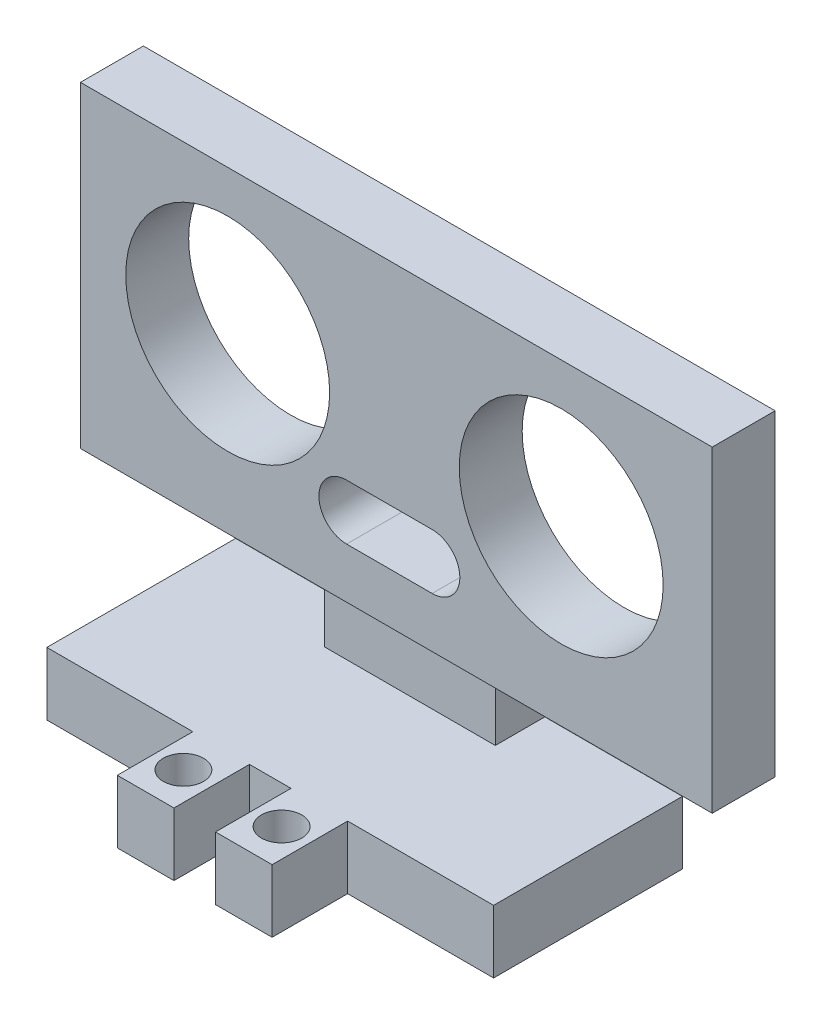
SolidWorks part; units mm, degrees
ref_plane "Front Plane" through (0, 0, 0) normal (0, 0, 1) x (1, 0, 0)
ref_plane "Top Plane" through (0, 0, 0) normal (0, 1, 0) x (1, 0, 0)
ref_plane "Right Plane" through (0, 0, 0) normal (1, 0, 0) x (0, 0, -1)
sketch "Sketch1" plane through (0, 0, 0) normal (0, 1, 0) x (1, 0, 0)
  line L0 (12.7692, 9.9599) -> (48.2692, 9.9599)
  line L5 (12.7692, 21.2754) -> (24.3692, 21.2754)
  line L10 (12.7692, 21.2754) -> (12.7692, 6.2754)
  line L11 (12.7692, 6.2754) -> (24.3692, 6.2754)
  line L12 (48.2692, 21.2754) -> (48.2692, 6.2754)
  line L13 (12.7692, 14.0701) -> (48.2692, 14.1179)
  line L21 (28.8692, 21.2754) -> (32.1692, 21.2754)
  line L22 (36.6692, 21.2754) -> (48.2692, 21.2754)
  line L23 (24.3692, 21.2754) -> (28.8692, 21.2754)
  line L24 (32.1692, 21.2754) -> (36.6692, 21.2754)
  line L25 (24.3692, 0.2754) -> (24.3692, 6.2754)
  line L26 (24.3692, 0.2754) -> (28.8692, 0.2754)
  line L27 (28.8692, 0.2754) -> (28.8692, 6.2754)
  line L28 (32.1692, 0.2754) -> (32.1692, 6.2754)
  line L29 (32.1692, 0.2754) -> (36.6692, 0.2754)
  line L30 (36.6692, 0.2754) -> (36.6692, 6.2754)
  line L31 (28.8692, 6.2754) -> (32.1692, 6.2754)
  line L32 (36.6692, 6.2754) -> (48.2692, 6.2754)
  dimension "D3" = 3.3
  dimension "D4" = 11.6
  dimension "D5" = 4.5
  dimension "D6" = 4.5
  dimension "D1" = 35.5
  dimension "D2" = 15
  dimension "D7" = 6
  dimension "D8" = 6
extrude "Boss-Extrude7" add sketch "Sketch1" along normal blind 5 contours L13 L12 L5 L10 | L13 L10 L0 L12 | L0 L10 L11 L12 region at (30.5534, 0, -12.0269) region at (30.5192, 0, -6.7027) region at (30.4995, 0, -17.6847)
sketch "Sketch5" plane through (0, 5, 0) normal (0, 1, 0) x (1, 0, 0)
  line L0 (12.7692, 21.2754) -> (48.2692, 21.2754) construction
  line L1 (23.7692, 21.2754) -> (37.3363, 21.2754)
  line L2 (23.7692, 21.2754) -> (23.7692, 17.3426)
  line L3 (23.7692, 17.3426) -> (37.3363, 17.3426)
  line L4 (37.3363, 21.2754) -> (37.3363, 17.3426)
  line L5 (12.7692, 21.2754) -> (12.7692, 6.2754) construction
  dimension "D1" = 11
  dimension "D2" = 13.5671
extrude "Boss-Extrude8" add sketch "Sketch5" along normal blind 5
sketch "Sketch6" plane through (1.1246, 10, 0) normal (0, 1, 0) x (1, 0, 0)
  line L0 (11.6446, 21.2754) -> (11.6446, 6.2754) construction
  line L2 (4.2946, 21.2948) -> (54.4946, 21.2948)
  line L3 (4.2946, 21.2948) -> (4.2946, 16.2948)
  line L4 (4.2946, 16.2948) -> (54.4946, 16.2948)
  line L5 (54.4946, 21.2948) -> (54.4946, 16.2948)
  dimension "D1" = 50.2
  dimension "D2" = 5
  dimension "D3" = 7.35
extrude "Boss-Extrude9" add sketch "Sketch6" along normal blind 25.2 contours L3 L2 L5 L4
sketch "Sketch7" plane through (0, 0, -16.2948) normal (0, 0, 1) x (1, 0, 0)
  line L0 (17.1192, 23.75) -> (43.6192, 23.75)
  line L1 (5.4192, 10) -> (55.6192, 10) construction
  line L2 (26.5664, 16.2) -> (33.3664, 16.2) construction
  line L3 (26.5664, 18.4) -> (33.3664, 18.4)
  line L4 (26.5664, 14) -> (33.3664, 14)
  line L5 (55.6192, 35.2) -> (55.6192, 10) construction
  circle A0 centre (17.1192, 23.75) radius 8.1
  circle A1 centre (43.6192, 23.75) radius 8.1
  arc A2 (26.5664, 18.4) -> (26.5664, 14) centre (26.5664, 16.2) ccw
  arc A3 (33.3664, 14) -> (33.3664, 18.4) centre (33.3664, 16.2) ccw
  point P8 (29.9664, 16.2)
  dimension "D1" = 16.2
  dimension "D4" = 2.2
  dimension "D7" = 12
  dimension "D2" = 26.5
  dimension "D3" = 6.8
  dimension "D5" = 5.35
  dimension "D6" = 4
  dimension "D8" = 10.2528
extrude "Cut-Extrude1" cut sketch "Sketch7" against normal blind 10 contours A0 | A1 region at (43.6192, 31.6209, -16.2948) region at (9.2483, 23.75, -16.2948)
extrude "Cut-Extrude2" cut sketch "Sketch7<3>" against normal blind 10 contours L4 A3 L3 A2 region at (29.9664, 16.2, -16.2948)
sketch "Sketch7<3>" plane through (0, 0, -16.2948) normal (0, 0, 1) x (1, 0, 0) same geometry as "Sketch7"
sketch "Sketch9" plane through (0, 5, 0) normal (0, 1, 0) x (1, 0, 0)
  line L0 (32.1692, 3.2754) -> (36.6692, 3.2754) construction
  line L3 (24.3692, 3.2754) -> (28.8692, 3.2754) construction
  line L4 (24.3692, 0.2754) -> (24.3692, 6.2754) construction
  line L5 (28.8692, 0.2754) -> (28.8692, 6.2754) construction
  line L6 (32.1692, 0.2754) -> (32.1692, 6.2754) construction
  line L7 (36.6692, 0.2754) -> (36.6692, 6.2754) construction
  circle A0 centre (26.6192, 3.2754) radius 1.6
  circle A1 centre (34.4192, 3.2754) radius 1.6
  dimension "D1" = 3.2
  dimension "D2" = 3.2
extrude "Cut-Extrude4" cut sketch "Sketch9" against normal blind 10 contours A0 | A1
